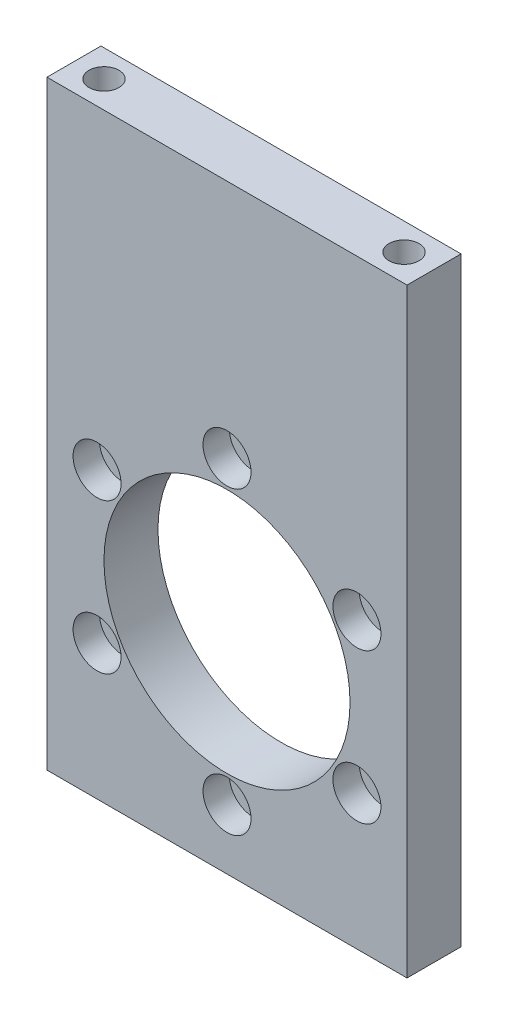
SolidWorks part; units mm, degrees
material "1060 Alloy"
ref_plane "Front Plane" through (0, 0, 0) normal (0, 0, 1) x (1, 0, 0)
ref_plane "Top Plane" through (0, 0, 0) normal (0, 1, 0) x (1, 0, 0)
ref_plane "Right Plane" through (0, 0, 0) normal (1, 0, 0) x (0, 0, -1)
sketch "Sketch1" plane through (0, 0, 0) normal (0, 0, 1) x (1, 0, 0)
  line L1 (0, 0) -> (60, 0)
  line L2 (0, 0) -> (0, 100)
  line L3 (0, 100) -> (60, 100)
  line L4 (60, 0) -> (60, 100)
  dimension "D1" = 60
  dimension "D2" = 100
extrude "Boss-Extrude1" add sketch "Sketch1" along normal mid plane 9
sketch "Sketch3" plane through (0, 0, 0) normal (0, 0, 1) x (1, 0, 0)
  circle A0 centre (30, 35) radius 20.5
  dimension "D1" = 41
  dimension "D2" = 30
  dimension "D3" = 35
extrude "Cut-Extrude2" cut sketch "Sketch3" against normal through all both and the other way through all
hole_wizard "M6 Tapped Hole1" positions "Sketch4" profile "Sketch5" tap size "M6" standard "ISO"
sketch "Sketch4" plane through (0, 0, 0) normal (0, -1, 0) x (-1, 0, 0)
  line L0 (-60, -4.5) -> (-60, 4.5) construction
  line L1 (0, -4.5) -> (0, 4.5) construction
  point P0 (-55, 0)
  point P2 (-5, 0)
  dimension "D1" = 5
  dimension "D2" = 5
sketch "Sketch5" plane through (55, 0, 0) normal (1, 0, 0) x (0, 0, -1)
  line L0 (0, 0) -> (0, 16.5022)
  line L1 (0, 16.5022) -> (2.5, 15)
  line L2 (2.5, 15) -> (2.5, 0)
  line L5 (2.5, 0) -> (0, 0)
  line L10 (0, 16.5022) -> (-2.5, 15) construction
  line L11 (0, -6.35) -> (0, 107.95) construction
  dimension "Tap Drill Dia." = 5
  dimension "Tap Drill Depth" = 15
  dimension "Drill Angle" = 118
cosmetic thread "Hole Thread1" parameters "D1"=12, "D2"=6
cosmetic thread "Hole Thread2" parameters "D1"=12, "D2"=6
ref_plane "Plane1" through (0, 50, 0) normal (0, 1, 0) x (1, 0, 0)
mirror "Mirror1" about plane through (0, 50, 0) normal (0, 1, 0) of "M6 Tapped Hole1"
hole_wizard "CBORE for M4 Hex Socket Head Cap Screw1" positions "Sketch6" profile "Sketch7" counterbore size "M4" standard "ISO" end condition through all
sketch "Sketch6" plane through (0, 0, 4.5) normal (0, 0, 1) x (1, 0, 0)
  line L0 (9.5, 35) -> (50.5, 35) construction
  circle A0 centre (30, 35) radius 20.5 construction
  point P0 (30, 60)
  point P16 (30, 35)
  dimension "D1" = 25
sketch "Sketch7" plane through (30, 60, 4.5) normal (1, 0, 0) x (0, -1, 0)
  line L0 (0, 0) -> (0, 9)
  line L1 (0, 9) -> (2.15, 9)
  line L3 (2.15, 9) -> (2.15, 4.4)
  line L4 (2.15, 4.4) -> (4, 4.4)
  line L5 (4, 4.4) -> (4, 0)
  line L7 (4, 0) -> (0, 0)
  line L11 (0, -6.35) -> (0, 107.95) construction
  dimension "Thru Hole Dia." = 4.3
  dimension "Thru Hole Depth" = 9
  dimension "C'Bore Dia." = 8
  dimension "C'Bore Depth" = 4.4
pattern_circular "CirPattern1" count 6 over 360 about axis through (30, 35, -4.5) along (0, 0, 1) of "CBORE for M4 Hex Socket Head Cap Screw1"
move or copy body "Body-Move/Copy1" [suppressed] bodies to move or copy 113
